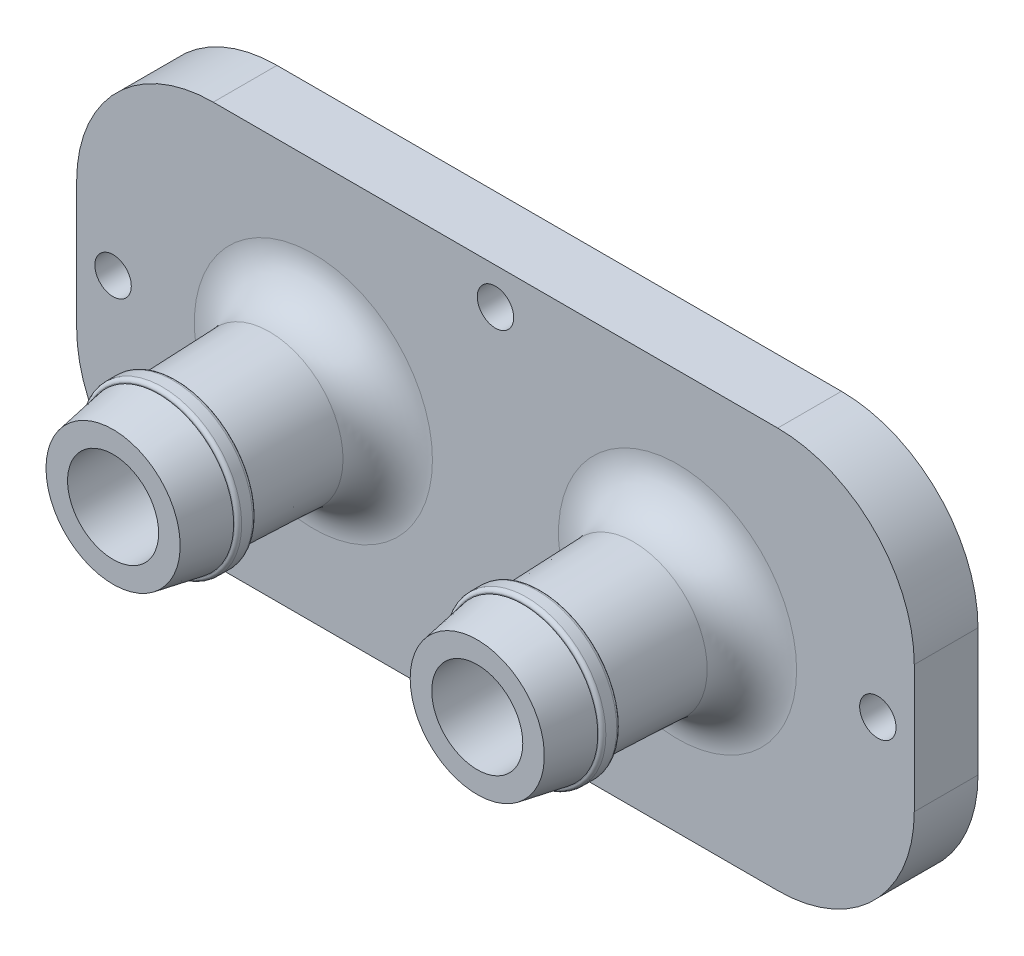
SolidWorks part; units mm, degrees
ref_plane "Front Plane" through (0, 0, 0) normal (0, 0, 1) x (1, 0, 0)
ref_plane "Top Plane" through (0, 0, 0) normal (0, 1, 0) x (1, 0, 0)
ref_plane "Right Plane" through (0, 0, 0) normal (1, 0, 0) x (0, 0, -1)
sketch "Sketch1" plane through (0, 0, 0) normal (0, 0, 1) x (1, 0, 0)
  line L0 (-38.0465, 0) -> (47.5349, 0) construction
  line L1 (0, 0) -> (0, 26.093) construction
  line L3 (-46, 22) -> (46, 22)
  line L4 (-46, 22) -> (-46, -22)
  line L5 (-46, -22) -> (46, -22)
  line L6 (46, 22) -> (46, -22)
  circle A0 centre (20, 0) radius 17
  circle A1 centre (-20, 0) radius 17
  dimension "D2" = 34
  dimension "D1" = 40
  dimension "D3" = 26
  dimension "D4" = 22
extrude "Boss-Extrude1" add sketch "Sketch1" along normal blind 4
fillet "Fillet1" radius 15 4 edges at (-46, -22, 2) (46, -22, 2) (46, 22, 2) (-46, 22, 2)
sketch "Sketch2" plane through (0, 0, 4) normal (0, 0, 1) x (1, 0, 0)
  line L8 (-46, 7) -> (-46, -7)
  line L9 (-31, -22) -> (31, -22)
  line L10 (46, -7) -> (46, 7)
  line L11 (31, 22) -> (-31, 22)
  line L12 (-46, 7) -> (-46, -7)
  line L13 (-31, -22) -> (31, -22)
  line L14 (46, -7) -> (46, 7)
  line L15 (31, 22) -> (-31, 22)
  circle A4 centre (-20, 0) radius 5
  circle A5 centre (-20, 0) radius 17 construction
  circle A6 centre (20, 0) radius 5
  circle A7 centre (20, 0) radius 17 construction
  arc A8 (-31, 22) -> (-46, 7) centre (-31, 7) ccw
  arc A9 (-46, -7) -> (-31, -22) centre (-31, -7) ccw
  arc A10 (31, -22) -> (46, -7) centre (31, -7) ccw
  arc A11 (46, 7) -> (31, 22) centre (31, 7) ccw
  arc A12 (-31, 22) -> (-46, 7) centre (-31, 7) ccw
  arc A13 (-46, -7) -> (-31, -22) centre (-31, -7) ccw
  arc A14 (31, -22) -> (46, -7) centre (31, -7) ccw
  arc A15 (46, 7) -> (31, 22) centre (31, 7) ccw
  dimension "D2" = 10
  dimension "D1" = 0
extrude "Boss-Extrude2" add sketch "Sketch2" along normal blind 3
sketch "Sketch3" plane through (0, 0, 7) normal (0, 0, 1) x (1, 0, 0)
  circle A0 centre (-20, 0) radius 7.25
  circle A1 centre (20, 0) radius 7.25
  circle A2 centre (20, 0) radius 5
  circle A3 centre (-20, 0) radius 5
  circle A4 centre (-20, 0) radius 5 construction
  dimension "D1" = 14.5
extrude "Boss-Extrude3" add sketch "Sketch3" along normal blind 15
chamfer "Chamfer1" distance 1 angle 88 2 edges at (-12.75, 0, 7) (27.25, 0, 7) first distance on face at (-12.75, 0, 7)
fillet "Fillet2" radius 2 2 edges at (-3, 0, 4) (37, 0, 4)
fillet "Fillet3" radius 10 2 edges at (-15, 0, 4) (25, 0, 4)
fillet "Fillet4" radius 5 2 edges at (28.25, 0, 7) (-11.75, 0, 7)
sketch "Sketch4" plane through (0, 0, 22) normal (0, 0, 1) x (1, 0, 0)
  circle A0 centre (-20, 0) radius 5
  circle A1 centre (-20, 0) radius 8.7262
  circle A2 centre (20, 0) radius 5
  circle A3 centre (20, 0) radius 8.7262
  circle A4 centre (20, 0) radius 7.7262 construction
  circle A5 centre (-20, 0) radius 5 construction
  circle A6 centre (20, 0) radius 5 construction
  dimension "D1" = 1
extrude "Boss-Extrude4" add sketch "Sketch4" along normal blind 2
sketch "Sketch6" plane through (0, 0, 24) normal (0, 0, 1) x (1, 0, 0)
  circle A0 centre (20, 0) radius 5
  circle A1 centre (20, 0) radius 7.25
  circle A2 centre (-20, 0) radius 7.25
  circle A3 centre (-20, 0) radius 5
  circle A4 centre (-20, 0) radius 5 construction
  dimension "D1" = 14.5
extrude "Boss-Extrude5" add sketch "Sketch6" along normal blind 5
fillet "Fillet5" radius 0.4 6 edges at (27.7262, 0, 22) (28.7262, 0, 22) (28.7262, 0, 24) (-12.2738, 0, 22) (-11.2738, 0, 22) (-11.2738, 0, 24)
chamfer "Chamfer2" distance 1 angle 80 2 edges at (27.25, 0, 24) (-12.75, 0, 24) first distance on face at (28.3262, 0, 24) first distance on face at (-11.6738, 0, 24)
sketch "Sketch8" plane through (0, 0, 7) normal (0, 0, 1) x (1, 0, 0)
  line L0 (0, 0) -> (0, 39.11) construction
  line L1 (0, 0) -> (65.4286, 0) construction
  circle A0 centre (0, 18) radius 2
  circle A1 centre (0, -18) radius 2
  circle A2 centre (42, 0) radius 2
  circle A3 centre (-42, 0) radius 2
  dimension "D1" = 4
  dimension "D2" = 84
  dimension "D3" = 36
extrude "Cut-Extrude1" cut sketch "Sketch8" against normal through all
